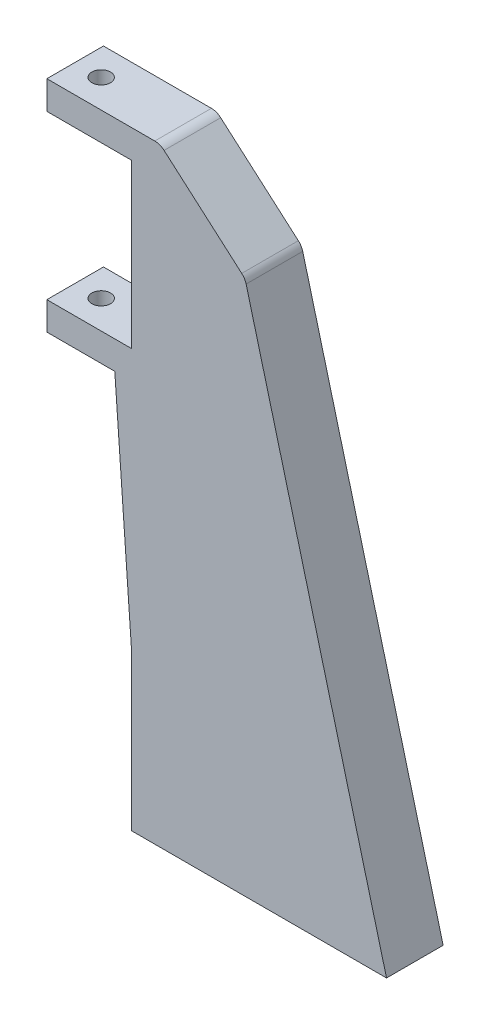
SolidWorks part; units mm, degrees
ref_plane "Front Plane" through (0, 0, 0) normal (0, 0, 1) x (1, 0, 0)
ref_plane "Top Plane" through (0, 0, 0) normal (0, 1, 0) x (1, 0, 0)
ref_plane "Right Plane" through (0, 0, 0) normal (1, 0, 0) x (0, 0, -1)
sketch "Sketch1" plane through (0, 0, 0) normal (0, 0, 1) x (1, 0, 0)
  line L0 (0, 0) -> (0, 12.7)
  line L1 (0, 12.7) -> (50.8, 12.7)
  line L2 (50.8, 12.7) -> (88.9, -20.5102)
  line L3 (0, 0) -> (38.0187, 0)
  line L4 (38.0187, 0) -> (38.0187, -73.1523)
  line L5 (38.0187, -73.1523) -> (0, -73.1523)
  line L6 (0, -73.1523) -> (0, -85.7639)
  line L7 (0, -85.7639) -> (30.48, -85.7639)
  line L10 (38.0187, -260.5159) -> (152.4, -260.5159)
  line L11 (152.4, -260.5159) -> (88.9, -20.5102)
  line L15 (30.48, -85.7639) -> (38.0187, -190.6965)
  line L16 (38.0187, -190.6965) -> (38.0187, -260.5159)
  dimension "D1" = 50.8
  dimension "D2" = 12.7
  dimension "D3" = 38.0187
  dimension "D4" = 73.1523
  dimension "D5" = 152.4
  dimension "D6" = 38.1
  dimension "D7" = 30.48
  dimension "D9" = 12.6117
  dimension "D10" = 174.752
extrude "Boss-Extrude1" add sketch "Sketch1" along normal blind 25.4
sketch "Sketch2" plane through (0, 0, 0) normal (0, 0, -1) x (-1, 0, 0)
  line L0 (0, -85.7639) -> (-30.48, -85.7639) construction
  line L1 (-101.5187, -144.4379) -> (-63.4187, -144.4379)
  line L2 (-101.5187, -144.4379) -> (-101.5187, -182.5379)
  line L3 (-101.5187, -182.5379) -> (-63.4187, -182.5379)
  line L4 (-63.4187, -144.4379) -> (-63.4187, -182.5379)
  line L5 (-38.0187, -190.6965) -> (-38.0187, -260.5159) construction
  dimension "D1" = 38.1
  dimension "D2" = 38.1
  dimension "D3" = 58.674
  dimension "D4" = 25.4
extrude "Cut-Extrude1" cut sketch "Sketch2" against normal offset from surface (12.7 mm away) 12.7 up to face at (39.5546, -85.3892, 25.4)
sketch "Sketch3" plane through (0, 12.7, 0) normal (0, 1, 0) x (1, 0, 0)
  line L0 (0, -25.4) -> (0, 0) construction
  line L1 (50.8, -25.4) -> (0, -25.4) construction
  circle A0 centre (11.684, -12.7) radius 4.191
  dimension "D1" = 8.382
  dimension "D2" = 11.684
  dimension "D3" = 12.7
extrude "Cut-Extrude2" cut sketch "Sketch3" against normal through all
sketch "Sketch4" plane through (0, -260.5159, 0) normal (0, -1, 0) x (-1, 0, 0)
  line L0 (-38.0187, -25.4) -> (-152.4, -25.4) construction
  line L1 (-152.4, -25.4) -> (-152.4, 0) construction
  circle A0 centre (-139.7, -12.7) radius 4.191
  circle A1 centre (-63.5, -11.8166) radius 4.191
  dimension "D3" = 8.382
  dimension "D4" = 8.382
  dimension "D1" = 12.7
  dimension "D2" = 12.7
  dimension "D5" = 76.2
extrude "Cut-Extrude3" cut sketch "Sketch4" against normal blind 25.4
fillet "Fillet1" radius 6.35 3 edges at (38.0187, -190.6965, 12.7) (88.9, -20.5102, 12.7) (50.8, 12.7, 12.7)
fillet "Fillet2" radius 3.175 4 edges at (101.5187, -182.5379, 6.35) (63.4187, -182.5379, 6.35) (63.4187, -144.4379, 6.35) (101.5187, -144.4379, 6.35)
